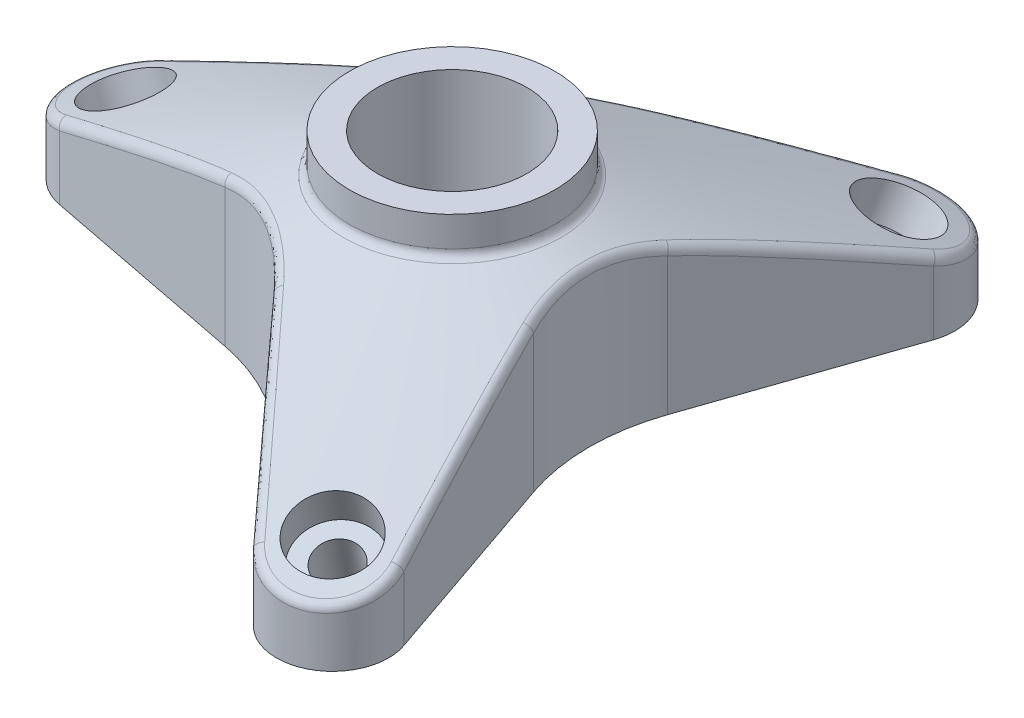
SolidWorks part; units mm, degrees
ref_plane "Front Plane" through (0, 0, 0) normal (0, 0, 1) x (1, 0, 0)
ref_plane "Top Plane" through (0, 0, 0) normal (0, 1, 0) x (1, 0, 0)
ref_plane "Right Plane" through (0, 0, 0) normal (1, 0, 0) x (0, 0, -1)
sketch "Sketch1" plane through (0, 0, 0) normal (0, 1, 0) x (1, 0, 0)
  line L0 (-36.1449, 5.8898) -> (-14.1405, 10.167)
  line L1 (-36.1449, -5.8898) -> (-14.1405, -10.167)
  line L2 (-35, 0) -> (0, 0) construction
  line L3 (23.1731, 28.3575) -> (15.8751, 7.1625)
  line L4 (12.9717, 34.2472) -> (-1.7346, 17.3295)
  line L5 (12.9717, -34.2472) -> (-1.7346, -17.3295)
  line L6 (23.1731, -28.3575) -> (15.8751, -7.1625)
  circle A0 centre (0, 0) radius 8
  circle A1 centre (0, 0) radius 11
  circle A4 centre (-35, 0) radius 6
  circle A7 centre (17.5, 30.3109) radius 6
  circle A8 centre (17.5, -30.3109) radius 6
  arc A9 (-1.7346, 17.3295) -> (-14.1405, 10.167) centre (-18.3383, 31.7628) cw
  circle A10 centre (0, 0) radius 35 construction
  arc A11 (15.8751, -7.1625) -> (15.8751, 7.1625) centre (36.6765, 0) cw
  arc A12 (-14.1405, -10.167) -> (-1.7346, -17.3295) centre (-18.3383, -31.7628) cw
  point P24 (0, 0)
  point P26 (0, 0)
  point P28 (20.7603, -43.2069)
  point P29 (26.6699, -38.5128)
  point P30 (0, 0)
  point P31 (0, 0)
  dimension "D1" = 16
  dimension "D2" = 22
  dimension "D3" = 12
  dimension "D7" = 22
  dimension "D8" = 22
  dimension "D9" = 22
  dimension "D10" = 70
  dimension "D4" = 22
  dimension "D5" = 11
  dimension "D6" = 3
extrude "Boss-Extrude1" add sketch "Sketch1" along normal blind 22 contours A1 A0 | L1 A12 L5 A8 L6 A11 L3 A7 L4 A9 L0 A4 A1 | A7 | A8 | A4 region at (-24.9698, 0, -7.1389) region at (-35, 0, 0) region at (17.5, 0, -30.3109) region at (17.5, 0, 30.3109) region at (-10.6889, 0, 0)
sketch "Sketch2" plane through (0, 0, 0) normal (0, 0, 1) x (1, 0, 0)
  line L1 (-1.7346, 22) -> (-14.1405, 22) construction
  line L2 (0, 22.5651) -> (-41, 6)
  line L3 (-41, 22) -> (-41, 0) construction
  line L4 (-41, 6) -> (-41, 0)
  line L5 (-41, 0) -> (0, 0)
  line L6 (-14.1405, 0) -> (-1.7346, 0) construction
  line L9 (0, 22) -> (0, 0) construction
  line L12 (-41, 6) -> (-41, 22)
  line L13 (-41, 22) -> (0, 22)
  line L14 (12.9717, 22) -> (-1.7346, 22) construction
  line L15 (0, 0) -> (0, 22)
  dimension "D1" = 112
  dimension "D2" = 6
revolve "Cut-Revolve1" cut sketch "Sketch2" angle 360 about L15 region at (-27.7995, 16.6667, 0)
extrude "Boss-Extrude2" add sketch "Sketch1<3>" along normal blind 22 contours A1 A0 region at (-10.6889, 0, 0)
sketch "Sketch1<3>" plane through (0, 0, 0) normal (0, 1, 0) x (1, 0, 0) same geometry as "Sketch1"
hole_wizard "CBORE for M4 SHCS1" positions "3DSketch1" profile "Sketch4" counterbore size "M4" standard "ANSI Metric" end condition up to next
sketch3d "3DSketch1"
  point P0 (-35, 8.4242, 0)
  point P2 (17.5, 8.4242, -30.3109)
  point P4 (17.5, 8.4242, 30.3109)
  point P9 (0, 0, 0)
  point P11 (0, 0, 0)
sketch "Sketch4" plane through (-35, 8.4242, 0) normal (0, 0, 1) x (-0.9272, -0.3746, 0)
  line L0 (0, 0) -> (0, 9.0857)
  line L1 (0, 9.0857) -> (2.25, 9.0857)
  line L3 (2.25, 9.0857) -> (2.25, 4)
  line L4 (2.25, 4) -> (4, 4)
  line L5 (4, 4) -> (4, 0)
  line L7 (4, 0) -> (0, 0)
  line L11 (0, -6.35) -> (0, 107.95) construction
  dimension "Thru Hole Dia." = 4.5
  dimension "Thru Hole Depth" = 9.0857
  dimension "C'Bore Dia." = 8
  dimension "C'Bore Depth" = 4
fillet "Fillet1" radius 1 13 edges at (14.7063, 16.6054, -1.1449) (20.5192, 6, -35.4959) (-8.3446, 16.6054, -12.1636) (-41, 6, -0.0223) (-6.3616, 16.6054, 13.3085) (20.4807, 6, 35.5182) (0, 18.1208, -11)
